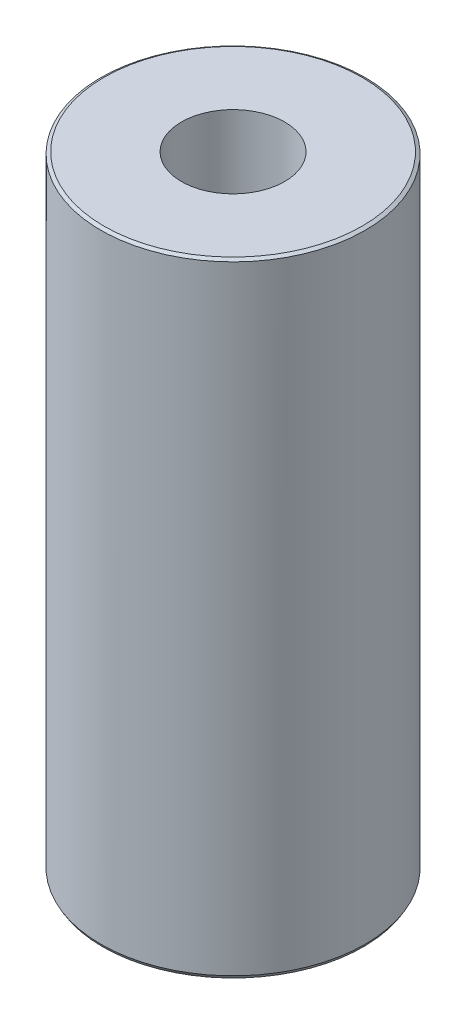
SolidWorks part; units mm, degrees
ref_plane "Front Plane" through (0, 0, 0) normal (0, 0, 1) x (1, 0, 0)
ref_plane "Top Plane" through (0, 0, 0) normal (0, 1, 0) x (1, 0, 0)
ref_plane "Right Plane" through (0, 0, 0) normal (1, 0, 0) x (0, 0, -1)
sketch "Sketch1" plane through (0, 0, 0) normal (0, 1, 0) x (1, 0, 0)
  circle A0 centre (0, 0) radius 25
  dimension "SHAFT_OD" = 50
extrude "Boss-Extrude1" add sketch "Sketch1" along normal blind 117.8541
sketch "Sketch2" plane through (0, 0, 0) normal (0, 1, 0) x (1, 0, 0)
  circle A0 centre (0, 0) radius 9.7617
  dimension "BORE_D" = 19.5235
extrude "Cut-Extrude1" cut sketch "Sketch2" along normal through all
chamfer "Chamfer1" distance 0.355 angle 60 2 edges at (0, 117.8541, 25) (0, 0, 25) first distance on face at (0, 117.8541, 25) first distance on face at (0, 0, 9.7617)
